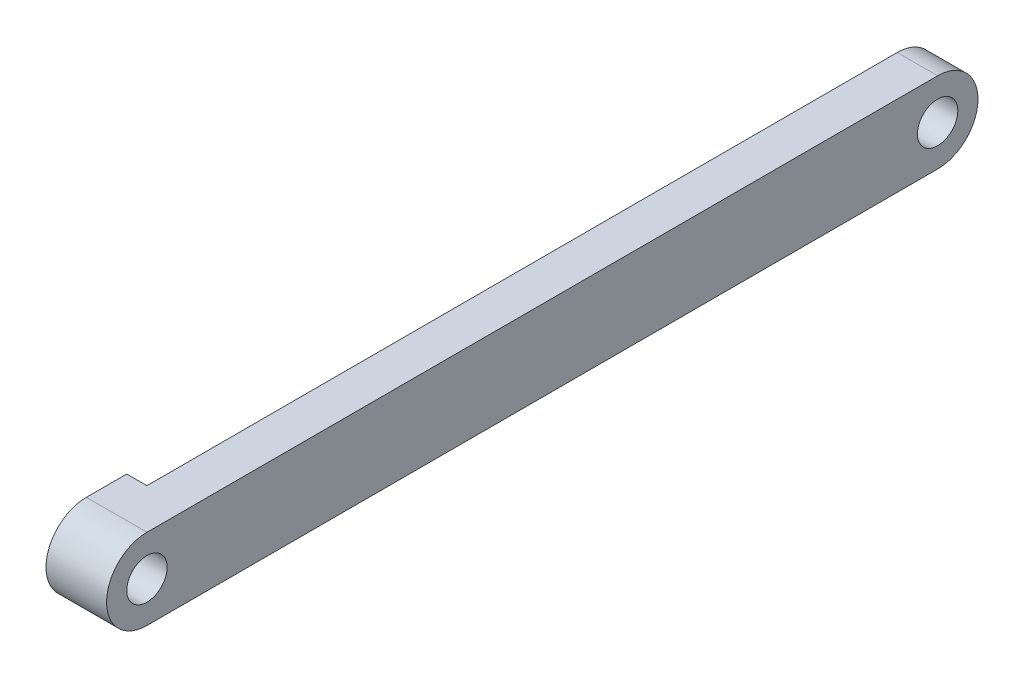
SolidWorks part; units mm, degrees
ref_plane "Front Plane" through (0, 0, 0) normal (0, 0, 1) x (1, 0, 0)
ref_plane "Top Plane" through (0, 0, 0) normal (0, 1, 0) x (1, 0, 0)
ref_plane "Right Plane" through (0, 0, 0) normal (1, 0, 0) x (0, 0, -1)
sketch "Sketch1" plane through (0, 0, 0) normal (1, 0, 0) x (0, 0, -1)
  line L0 (0, 0) -> (39.164, 0) construction
  line L1 (0, -2) -> (39.164, -2)
  line L18 (0, 2) -> (39.164, 2)
  arc A10 (0, -2) -> (0, 2) centre (0, 0) cw
  arc A11 (39.164, 2) -> (39.164, -2) centre (39.164, 0) cw
  circle A12 centre (0, 0) radius 1
  circle A13 centre (39.164, 0) radius 1
  dimension "D4" = 2
  dimension "D1" = 2
  dimension "D3" = 39.164
  dimension "D2" = 2
extrude "Boss-Extrude1" add sketch "Sketch1" along normal blind 3
sketch "Sketch2" plane through (0, 0, 0) normal (-1, 0, 0) x (0, 0, 1)
  line L0 (0, -2) -> (-39.164, -2) construction
  line L1 (-41.164, 2) -> (-2, 2)
  line L2 (-41.164, 2) -> (-41.164, -2)
  line L3 (-41.164, -2) -> (-2, -2)
  line L4 (-2, 2) -> (-2, -2)
  line L5 (-39.164, 2) -> (0, 2) construction
  arc A0 (0, -2) -> (0, 2) centre (0, 0) ccw construction
  arc A1 (-39.164, 2) -> (-39.164, -2) centre (-39.164, 0) ccw construction
  point P9 (2, 0)
  dimension "D1" = 4
extrude "Cut-Extrude1" cut sketch "Sketch2" against normal blind 1 contours L1 L4 L3 L2
